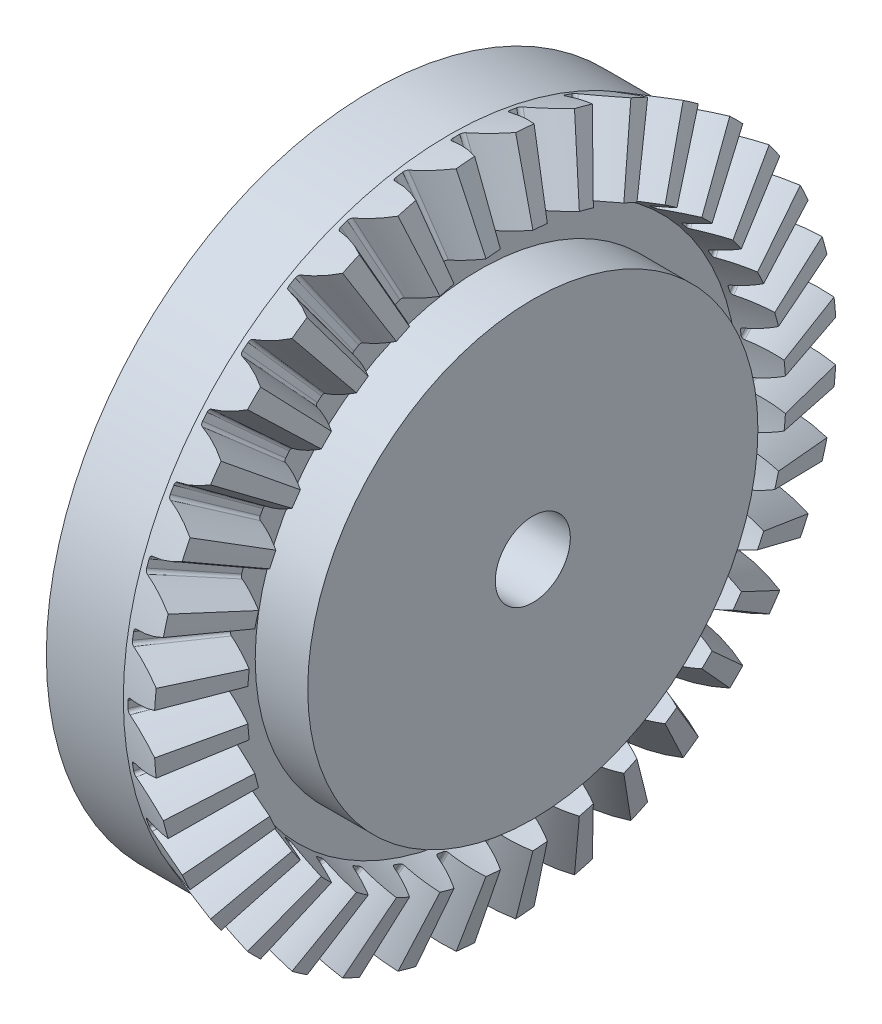
SolidWorks part; units mm, degrees
revolve "Base-Revolve" add sketch "BasProSke" angle 360 about L0 other way angle 5
sketch "BasProSke" plane through (0, 0, 0) normal (0, 1, 0) x (1, 0, 0)
  line L0 (-10, 0) -> (60, 0) construction
  line L1 (0, 0) -> (0, 8.684)
  line L2 (0, 0) -> (0.8323, 0)
  line L3 (0.8323, 0) -> (0.8323, 6.8532)
  line L4 (3.948, 0) -> (-9.0794, 39.0823) construction
  line L5 (0, 8.684) -> (1.2284, 9.0935)
  line L6 (3.948, 0) -> (-23.6442, 92.2592) construction
  line L7 (3.948, 0) -> (0, 8.684) construction
  line L8 (1.2284, 9.0935) -> (1.8018, 7.1764)
  line L9 (1.8018, 7.1764) -> (0.8323, 6.8532)
  line L10 (0.948, 9) -> (-11.0363, 9) construction
  dimension "D1" = 17.368
  dimension "D2" = 3.948
  dimension "D3" = 9.4868
  dimension "D4" = 1.784
ref_plane "Plane1" through (0, 0, 0) normal (0, 0, 1) x (1, 0, 0)
ref_plane "Plane2" through (0, 0, 0) normal (0, 1, 0) x (1, 0, 0)
ref_plane "Plane3" through (0, 0, 0) normal (1, 0, 0) x (0, 0, -1)
other "Configuration Table"
sketch "HoldingSke" plane through (0, 0, 0) normal (0, 1, 0) x (1, 0, 0)
  line L0 (0, 0) -> (1.618, -1.1756)
  line L1 (-15, 0) -> (100, 0) construction
  line L2 (0, 0) -> (-122.6628, 25.2748)
  line L3 (0, 0) -> (-11.863, 4.5341)
  line L4 (0, 0) -> (6.9867, 5.0761)
  line L5 (0, 0) -> (-5.6217, -2.0967)
  line L6 (0, 0) -> (-10.5278, -7.1032)
  line L7 (-122.6628, 25.2748) -> (-122.6177, 31.2747)
  line L8 (-76.2, 0.5) -> (-75.9, 0.5)
  line L9 (-71.009, 38.7566) -> (-53.1078, 45.2721)
  line L10 (-76.2, 71.12) -> (104.1128, 71.12)
  line L11 (0, 0) -> (-2, 0)
  line L12 (-76.2, 101.6) -> (-76.181, 101.6)
  line L13 (24.9733, 27.94) -> (52.9546, 28.2287)
  line L14 (24.9733, 27.94) -> (24.9743, 27.94)
  line L15 (24.9733, 27.94) -> (100.3893, 30.0425)
  line L16 (-122.6628, 25.2748) -> (3.6233, -1.5681)
  circle A0 centre (0, 0) radius 1
  circle A1 centre (0, 0) radius 8.684
  circle A2 centre (0, 0) radius 10
  circle A3 centre (0, 0) radius 1
  dimension "Num_teeth" = 36
  dimension "Pitch_radius" = 180.3128
  dimension "Width" = 2
ref_plane "ToothPln" through (0.6142, 8.8887, 0) normal (-0.3162, 0.9487, 0) x (0, 0, -1)
ref_plane "ToothPln2" through (0.3948, -1.1844, 0) normal (-0.3162, 0.9487, 0) x (0, 0, 1)
sketch "TooCutSke" plane through (0.6142, 8.8887, 0) normal (-0.3162, 0.9487, 0) x (0, 0, -1)
  line L2 (0, 8.6481) -> (144.0891, -1638.2981) construction
  line L3 (0, 8.6481) -> (78.8921, -1755.5054) construction
  line L4 (0, -15.621) -> (0, 105.791) construction
  line L6 (-24.765, -0.6474) -> (21.082, -0.6474) construction
  line L7 (0.7844, -0.3176) -> (0.4017, -0.3347) construction
  arc A0 (-0.6442, -0.8114) -> (0.6442, -0.8114) centre (0, 8.6481) ccw
  arc A1 (-0.094, 0.4481) -> (0.094, 0.4481) centre (0, 8.6481) ccw
  circle A2 centre (0, 8.6481) radius 9 construction
  circle A3 centre (0, 8.6481) radius 8.4572 construction
  arc A4 (0.1883, 0.3711) -> (0.094, 0.4481) centre (0.0951, 0.3531) ccw
  arc A5 (0.1883, 0.3711) -> (0.6442, -0.8114) centre (3.7229, 1.0544) ccw
  arc A6 (-0.6442, -0.8114) -> (-0.1883, 0.3711) centre (-3.7229, 1.0544) ccw
  arc A7 (-0.094, 0.4481) -> (-0.1883, 0.3711) centre (-0.0951, 0.3531) ccw
  ellipse E0 centre (0, 2.2282) end of major axis (9.0935, 2.2282) minor radius 2.8756 construction
sketch "TooCutSke2" plane through (0.3948, -1.1844, 0) normal (-0.3162, 0.9487, 0) x (0, 0, 1)
  line L0 (0, 0) -> (0, 68.072) construction
  line L2 (21.082, 2.7461) -> (-20.32, 2.7461) construction
  circle A0 centre (0, 3.7454) radius 0.0127
  ellipse E1 centre (0, 0) end of major axis (-8.684, 0) minor radius 2.7461 construction
loft "ToothCut" cut profiles "TooCutSke2", "TooCutSke"
pattern_circular "TeethCuts" count 36 every 10 about axis through (-10, 0, 0) along (1, 0, 0) of "ToothCut"
sketch "草图1" plane through (0.8323, 0, 0) normal (1, 0, 0) x (0, 0, -1)
  circle A0 centre (0, 0) radius 6
  dimension "D1" = 12
extrude "凸台-拉伸1" add sketch "草图1" along normal blind 1.4
sketch "HubSke" plane through (0, 0, 0) normal (-1, 0, 0) x (0, 0, 1)
  circle A0 centre (0, 0) radius 8.684
  dimension "Diameter" = 17.368
extrude "Hub" add sketch "HubSke" along normal blind 2.0521
sketch "BorSke" plane through (0, 0, 0) normal (1, 0, 0) x (0, 0, -1)
  circle A0 centre (0, 0) radius 1
  dimension "Diameter" = 2
extrude "Bore" cut sketch "BorSke" along normal mid plane 12.0001
sketch "KeySke" plane through (0, 0, 0) normal (1, 0, 0) x (0, 0, -1)
  line L0 (-0.4, 0) -> (-0.4, 1.3)
  line L1 (-0.4, 1.3) -> (0.4, 1.3)
  line L2 (0.4, 1.3) -> (0.4, 0)
  line L3 (0, 0) -> (0, 34) construction
  line L4 (-0.4, 0) -> (0.4, 0)
  dimension "Offset" = 1.3
extrude "Keyway" [suppressed] cut sketch "KeySke" along normal mid plane 12.0001
pattern_circular "Keyway2" [suppressed] count 2 every 90 about axis through (-10, 0, 0) along (1, 0, 0) reverse direction yes
equation "' \"Module@HoldingSke\" = 6.35"
equation "' \"Num_teeth@HoldingSke\" = 20"
equation "' \"Mating_teeth@HoldingSke\" = 12"
equation "' \"Ap@HoldingSke\" =  20"
equation "' \"Ap@HoldingSke\" = 20"
equation "' \"Width@HoldingSke\" = 0.5 * 25.4"
equation "' \"Hub_dia@HoldingSke\"= 2 * 25.4"
equation "' \"Hub_dia@HoldingSke\" = 2 * 25.4"
equation "' \"Mounting_dist@HoldingSke\" = 3 * 25.4"
equation "' \"Bore@HoldingSke\" = 19"
equation "' \"T_dim@HoldingSke\" = 0.1 * 25.4"
equation "' \"Width@KeySke\" = 0.25 * 25.4"
equation "' \"Show_teeth@HoldingSke\" = 100"
equation "' \"Backlash@HoldingSke\" = 0.009 * 25.4"
equation "' \"Addendum_fac@HoldingSke\" = 1.0"
equation "' \"Dedendum_fac@HoldingSke\" = 1.188"
equation "' \"Dedendum_add@HoldingSke\" = 0.002 * 25.4"
equation "' \"Clearance_fac@HoldingSke\" = 0.188"
equation "\"Pitch@HoldingSke\" = 1 / \"Module@HoldingSke\""
equation " \"Addendum_fac@HoldingSke\" = 0.54 + 0.46 / (\"Num_teeth@HoldingSke\" /  \"Mating_teeth@HoldingSke\" ) ^ 2"
equation "' \"Addendum_fac@HoldingSke\" = 2 - (0.54 + 0.46 / (\"Mating_teeth@HoldingSke\" /  \"Num_teeth@HoldingSke\" ) ^ 2)"
equation "\"Dedendum_fac@HoldingSke\" = 2.188 - \"Addendum_fac@HoldingSke\""
equation "\"Pitch_rad@BasProSke\" = \"Num_teeth@HoldingSke\" / \"Pitch@HoldingSke\" / 2"
equation "\"Pitch_ang@BasProSke\" = atn(\"Num_teeth@HoldingSke\" / \"Mating_teeth@HoldingSke\") * (180 / 3.14159265)"
equation "\"Addendum@BasProSke\" = \"Addendum_fac@HoldingSke\" / \"Pitch@HoldingSke\""
equation "\"Dedendum_plus@BasProSke\" = (\"Dedendum_fac@HoldingSke\" / \"Pitch@HoldingSke\" + \"Dedendum_add@HoldingSke\") * 1.25"
equation "\"Face_wid@BasProSke\" = \"Width@HoldingSke\""
equation "\"Radius@TooCutSke\" = ((\"Num_teeth@HoldingSke\" + 2 * \"Addendum_fac@HoldingSke\") / \"Pitch@HoldingSke\" ) / 2"
equation "\"Overcut_dia@TooCutSke\" =  1.02 * (\"Num_teeth@HoldingSke\" + 2 * \"Addendum_fac@HoldingSke\") / \"Pitch@HoldingSke\""
equation "\"Pitch_dia@TooCutSke\" = \"Num_teeth@HoldingSke\" / \"Pitch@HoldingSke\""
equation "\"Base_dia@TooCutSke\" = \"Num_teeth@HoldingSke\" / \"Pitch@HoldingSke\" * cos((\"Ap@HoldingSke\"  * 3.14159265 / 180))"
equation "'  \"Root_dia@TooCutSke\" =  (\"Num_teeth@HoldingSke\" + 2) / \"Pitch@HoldingSke\" - 2 * (\"Addendum_fac@HoldingSke\" + \"Dedendum_fac@HoldingSke\") / \"Pitch@HoldingSke\" - \"Dedendum_add@HoldingSke\" * 2"
equation "'  \"Root_dia@TooCutSke\" = (\"Num_teeth@HoldingSke\" + 2) / \"Pitch@HoldingSke\" - 2 * (\"Addendum_fac@HoldingSke\" + \"Dedendum_fac@HoldingSke\") / \"Pitch@HoldingSke\" - \"Dedendum_add@HoldingSke\" * 2"
equation "\"Root_dia@TooCutSke\" =  \"Num_teeth@HoldingSke\" / \"Pitch@HoldingSke\" -  2 * \"Dedendum_fac@HoldingSke\" / \"Pitch@HoldingSke\" - \"Dedendum_add@HoldingSke\" * 2"
equation "\"Half_ang@TooCutSke\" = 180 / \"Num_teeth@HoldingSke\""
equation "\"Half_CT@TooCutSke\" = \"Num_teeth@HoldingSke\" / \"Pitch@HoldingSke\" * sin((3.14159265 / 2 / \"Num_teeth@HoldingSke\")) / 2 - 2 * \"Backlash@HoldingSke\" / 4"
equation "\"Flank_rad@TooCutSke\" = \"Num_teeth@HoldingSke\" / \"Pitch@HoldingSke\" / 5"
equation "\"Root_fillet@TooCutSke\" = \"Clearance_fac@HoldingSke\" / \"Pitch@HoldingSke\" + \"Dedendum_add@HoldingSke\""
equation "\"Offset@ToothPln2\"  = \"Num_teeth@HoldingSke\" / \"Pitch@HoldingSke\" / 2 / sin(atn(\"Num_teeth@HoldingSke\" / \"Mating_teeth@HoldingSke\"))"
equation "\"Dedendum_plus@TooCutSke2\" = \"Dedendum_plus@BasProSke\""
equation "\"MHD@HoldingSke\" = \"Num_teeth@HoldingSke\" / \"Pitch@HoldingSke\" - 2 * \"Dedendum_plus@BasProSke\" * cos(atn(\"Num_teeth@HoldingSke\" / \"Mating_teeth@HoldingSke\"))"
equation "\"MBD@HoldingSke\" = \"Num_teeth@HoldingSke\" / \"Pitch@HoldingSke\" - 2 * \"Dedendum_plus@BasProSke\" * cos(atn(\"Num_teeth@HoldingSke\" / \"Mating_teeth@HoldingSke\")) - 0.002 * 25.4"
equation "\"MnMD@HoldingSke\" =  \"Num_teeth@HoldingSke\" / \"Pitch@HoldingSke\" / 2 / (\"Num_teeth@HoldingSke\" / \"Mating_teeth@HoldingSke\") + \"Dedendum_plus@BasProSke\" * sin(atn(\"Num_teeth@HoldingSke\" / \"Mating_teeth@HoldingSke\"))"
equation "\"OAL@HoldingSke\" = \"MnMD@HoldingSke\""
equation "\"MHD@HoldingSke\" = ((sgn( \"MHD@HoldingSke\" - \"Hub_dia@HoldingSke\" )-1)*( \"MHD@HoldingSke\" - \"Hub_dia@HoldingSke\" ))/-2+ \"Hub_dia@HoldingSke\""
equation "\"MBD@HoldingSke\" = ((sgn( \"MBD@HoldingSke\" - \"Bore@HoldingSke\" )-1)*( \"MBD@HoldingSke\" - \"Bore@HoldingSke\" ))/-2+ \"Bore@HoldingSke\""
equation "\"Face_wid@BasProSke\" = ((sgn( \"Face_wid@BasProSke\" - \"Offset@ToothPln2\" * 0.9)-1)*( \"Face_wid@BasProSke\" - \"Offset@ToothPln2\" * 0.9))/-2+ \"Offset@ToothPln2\" * 0.9"
equation "\"OAL@HoldingSke\" = ((sgn( \"OAL@HoldingSke\" - \"Mounting_dist@HoldingSke\" )+1)*( \"OAL@HoldingSke\" - \"Mounting_dist@HoldingSke\" ))/2 + \"Mounting_dist@HoldingSke\" + 0.000002 * 25.4"
equation "\"Num_teeth@TeethCuts\" = int( \"Show_teeth@HoldingSke\" ) + 1"
equation "\"Num_teeth@TeethCuts\" = ((sgn( \"Num_teeth@TeethCuts\" - \"Num_teeth@HoldingSke\" )-1)*( \"Num_teeth@TeethCuts\" - \"Num_teeth@HoldingSke\" ))/-2+ \"Num_teeth@HoldingSke\""
equation "\"Num_teeth@TeethCuts\" = ((sgn( \"Num_teeth@TeethCuts\" - 2.0)+1)*( \"Num_teeth@TeethCuts\" - 2.0))/2 +2.0"
equation "\"Angle@TeethCuts\" = 360.0 / \"Num_teeth@HoldingSke\""
equation "\"Diameter@HubSke\" = \"MHD@HoldingSke\""
equation "\"Length@Hub\" = \"OAL@HoldingSke\" - \"MnMD@HoldingSke\" + 0.000002 * 25.4"
equation "\"Diameter@BorSke\" = \"MBD@HoldingSke\""
equation "\"D1@Bore\" = \"OAL@HoldingSke\" * 2.0"
equation "\"D1@Keyway\" = \"OAL@HoldingSke\" * 2.0"
equation "\"Offset@KeySke\" = \"T_dim@HoldingSke\" + \"MBD@HoldingSke\" / 2.0"
